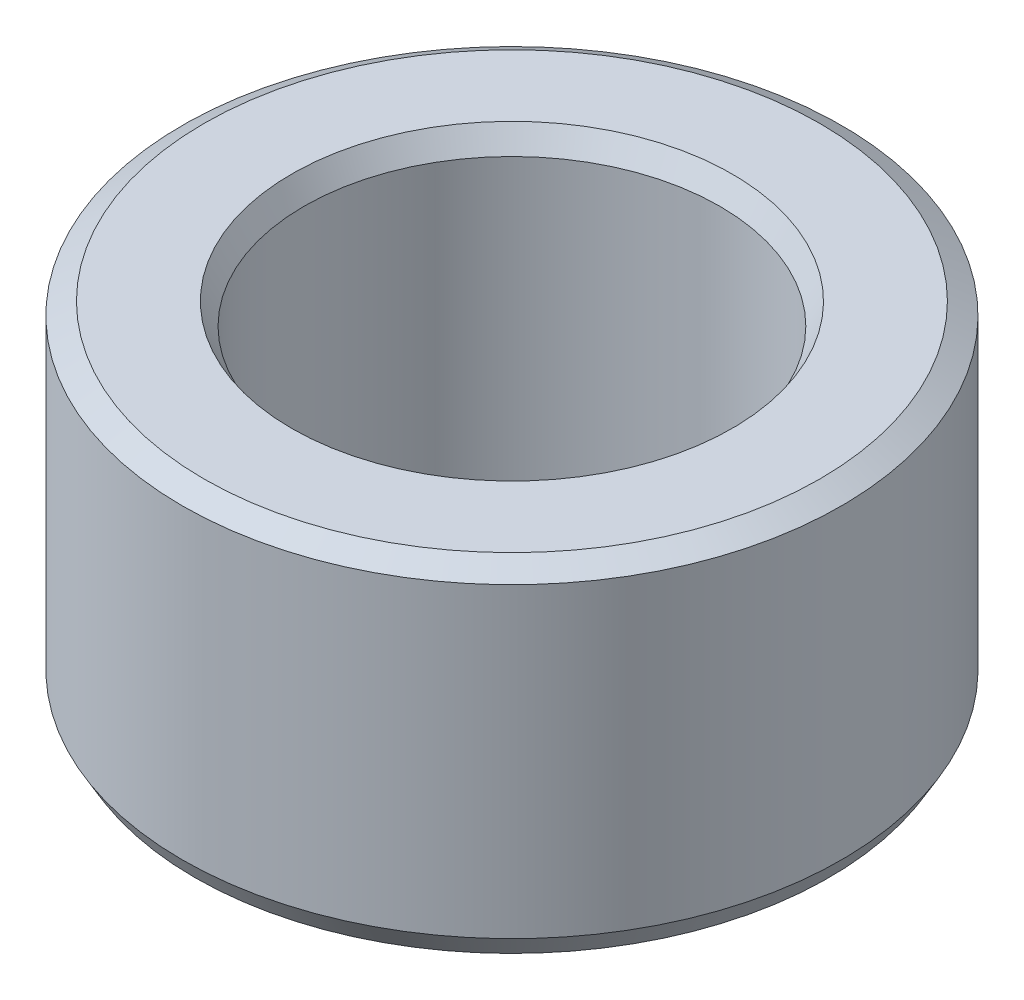
SolidWorks part; units mm, degrees
ref_plane "Front Plane" through (0, 0, 0) normal (0, 0, 1) x (1, 0, 0)
ref_plane "Top Plane" through (0, 0, 0) normal (0, 1, 0) x (1, 0, 0)
ref_plane "Right Plane" through (0, 0, 0) normal (1, 0, 0) x (0, 0, -1)
sketch "Sketch1" plane through (0, 0, 0) normal (0, 1, 0) x (1, 0, 0)
  circle A0 centre (0, 0) radius 20
  dimension "SLEEVE_OD" = 40
extrude "Boss-Extrude1" add sketch "Sketch1" along normal blind 20.6732
sketch "Sketch2" plane through (0, 0, 0) normal (0, 1, 0) x (1, 0, 0)
  circle A0 centre (0, 0) radius 12.6123
  dimension "BORE_D" = 25.2247
extrude "Cut-Extrude1" cut sketch "Sketch2" along normal through all
chamfer "Chamfer1" distance 0.7577 angle 60 4 edges at (0, 20.6732, 12.6123) (0, 0, 12.6123) (0, 0, 20) (0, 20.6732, 20) first distance on face at (0, 20.6732, 12.6123) first distance on face at (0, 0, 12.6123) first distance on face at (0, 20.6732, 20)
